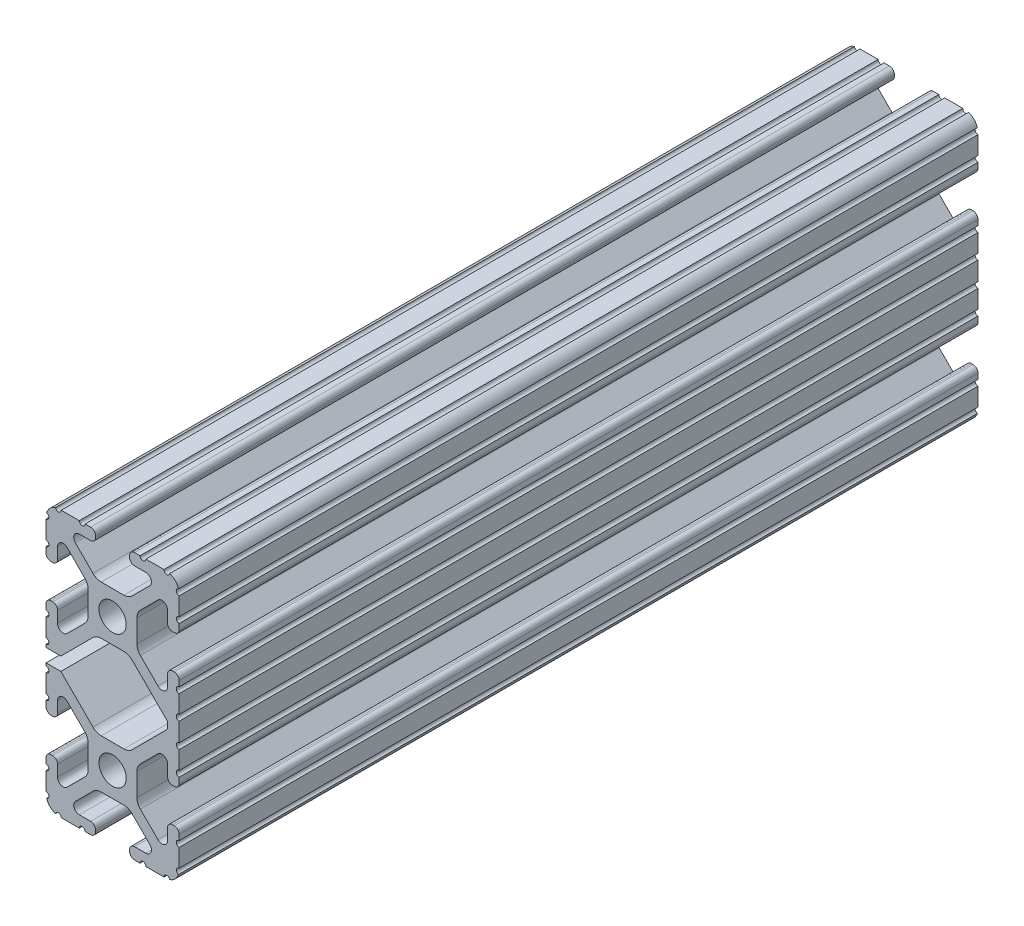
SolidWorks part; units mm, degrees
ref_plane "Front Plane" through (0, 0, 0) normal (0, 0, 1) x (1, 0, 0)
ref_plane "Top Plane" through (0, 0, 0) normal (0, 1, 0) x (1, 0, 0)
ref_plane "Right Plane" through (0, 0, 0) normal (1, 0, 0) x (0, 0, -1)
sketch "Sketch2" plane through (0, 0, 0) normal (0, 0, 1) x (1, 0, 0)
  line L0 (0, 25.4) -> (0, -25.4) construction
  line L1 (-12.7, 0) -> (12.7, 0) construction
  line L2 (3.2512, -25.4) -> (12.7, -25.4)
  line L3 (12.7, -25.4) -> (12.7, -15.9512)
  line L4 (3.2512, -25.4) -> (3.2512, -23.1902)
  line L5 (3.2512, -23.1902) -> (8.9276, -23.1902)
  line L6 (8.9276, -23.1902) -> (3.0856, -17.3482)
  line L7 (0, -12.7) -> (12.7, -25.4) construction
  line L8 (12.7, -15.9512) -> (10.4902, -15.9512)
  line L9 (10.4902, -15.9512) -> (10.4902, -21.6276)
  line L10 (10.4902, -21.6276) -> (4.6482, -15.7856)
  circle A0 centre (0, -12.7) radius 2.6035
  arc A1 (6.3485, -23.1902) -> (7.1039, -21.3665) centre (6.3485, -22.1219) ccw construction
  point P8 (0, -17.3482)
  dimension "Center Hole Diameter" = 5.207
  dimension "Rail Height" = 50.8
  dimension "Rail Width" = 25.4
  dimension "T-Slot Width" = 6.5024
  dimension "Slot Inner Width" = 14.8336
  dimension "Thickness" = 2.2098
  dimension "Slot Depth" = 5.842
  dimension "D1" = 2.2098
  dimension "C to C" = 25.4
sketch "Sketch3" plane through (0, 0, 0) normal (1, 0, 0) x (0, 0, -1)
  line L0 (-76.2, -25.4) -> (76.2, -25.4) construction
  line L1 (-50.8, 0) -> (50.8, 0) construction
  dimension "Length" = 152.4
sketch "Sketch4" plane through (0, 0, 0) normal (0, 0, 1) x (1, 0, 0)
  line L0 (4.1904, -25.4) -> (10.1173, -25.4)
  line L1 (3.2512, -25.4) -> (12.7, -25.4) construction
  line L2 (3.2512, -25.4) -> (3.2512, -23.1902) construction
  line L3 (3.2512, -23.1902) -> (8.9276, -23.1902) construction
  line L4 (3.2512, -24.1294) -> (3.2512, -24.4608)
  line L5 (4.1904, -23.1902) -> (6.3485, -23.1902)
  line L6 (0, -17.3482) -> (2.164, -17.3482)
  line L7 (8.9276, -23.1902) -> (3.0856, -17.3482) construction
  line L8 (3.7373, -17.9999) -> (7.1039, -21.3665)
  line L9 (12.7, -25.4) -> (12.7, -15.9512) construction
  line L10 (10.4902, -21.6276) -> (4.6482, -15.7856) construction
  line L11 (10.4902, -15.9512) -> (10.4902, -21.6276) construction
  line L12 (10.4902, -19.0485) -> (10.4902, -16.8904)
  line L13 (12.7, -15.9512) -> (10.4902, -15.9512) construction
  line L14 (11.4294, -15.9512) -> (11.7608, -15.9512)
  line L15 (12.7, -16.8904) -> (12.7, -22.8173)
  line L16 (8.6665, -19.8039) -> (5.2999, -16.4373)
  line L17 (4.6482, -12.7) -> (4.6482, -14.864)
  line L19 (0, -17.3482) -> (0, -15.3035)
  line L20 (0, 25.4) -> (0, -25.4) construction
  line L21 (4.6482, -12.7) -> (2.6035, -12.7)
  arc A0 (3.2512, -24.4608) -> (4.1904, -25.4) centre (4.1904, -24.4608) ccw
  circle A1 centre (0, -12.7) radius 2.6035 construction
  arc A2 (3.2512, -24.1294) -> (4.1904, -23.1902) centre (4.1904, -24.1294) cw
  arc A3 (6.3485, -23.1902) -> (7.1039, -21.3665) centre (6.3485, -22.1219) ccw
  arc A4 (2.164, -17.3482) -> (3.7373, -17.9999) centre (2.164, -19.5732) cw
  arc A5 (10.1173, -25.4) -> (12.7, -22.8173) centre (10.1173, -22.8173) ccw
  arc A6 (8.6665, -19.8039) -> (10.4902, -19.0485) centre (9.4219, -19.0485) ccw
  arc A7 (10.4902, -16.8904) -> (11.4294, -15.9512) centre (11.4294, -16.8904) cw
  arc A8 (11.7608, -15.9512) -> (12.7, -16.8904) centre (11.7608, -16.8904) cw
  arc A9 (5.2999, -16.4373) -> (4.6482, -14.864) centre (6.8732, -14.864) cw
  arc A11 (0, -15.3035) -> (2.6035, -12.7) centre (0, -12.7) ccw
  dimension "D1" = 2.5827
  dimension "D2" = 2.225
  dimension "D3" = 0.9392
extrude "Boss-Extrude1" add sketch "Sketch4" along normal mid plane 152.4
sketch "Sketch5" plane through (0, 0, 0) normal (0, 0, 1) x (1, 0, 0)
  line L0 (3.2512, -25.4) -> (12.7, -25.4) construction
  line L1 (4.1904, -23.1902) -> (6.3485, -23.1902) construction
  line L3 (0, -12.7) -> (12.7, -25.4) construction
  line L4 (6.3485, -23.1902) -> (6.3485, -25.4) construction
  line L5 (8.9276, -23.1902) -> (3.0856, -17.3482) construction
  circle A0 centre (10.3562, -25.4) radius 0.5524
  circle A1 centre (5.796, -25.4) radius 0.5524
  circle A2 centre (12.7, -23.0562) radius 0.5524
  circle A3 centre (12.7, -18.496) radius 0.5524
  point P10 (5.2694, -23.1902)
  point P12 (9.4219, -19.0485)
  dimension "D1" = 1.1049
extrude "Cut-Extrude1" cut sketch "Sketch5" against normal through all both and the other way through all
mirror "Mirror1" about plane through (4.6482, -12.7, 76.2) normal (0, -1, 0) of bodies 137 134
sketch "Sketch6" plane through (0, 0, 0) normal (0, 0, 1) x (1, 0, 0)
  line L0 (12.7, -1.7914) -> (12.7, 0)
  line L1 (12.7, 0) -> (9.8037, 0)
  line L2 (-12.7, 0) -> (12.7, 0) construction
  line L3 (9.8037, 0) -> (9.8037, -2.3438)
  line L4 (9.8037, -2.3438) -> (12.1476, -2.3438)
  circle A0 centre (12.7, -2.3438) radius 0.5524 construction
  arc A1 (12.7, -1.7914) -> (12.1476, -2.3438) centre (12.7, -2.3438) ccw
  arc A4 (12.58, -1.8046) -> (12.7, -2.8963) centre (12.7, -2.3438) ccw construction
  arc A6 (9.8037, 0) -> (10.8954, -0.12) centre (10.3562, 0) ccw construction
extrude "Boss-Extrude2" add sketch "Sketch6" along normal mid plane 152.4
sketch "Sketch7" plane through (0, 0, 0) normal (0, 0, 1) x (1, 0, 0)
  line L0 (5.4206, -5.7168) -> (10.3284, -0.809)
  line L1 (3.7373, -7.4001) -> (7.1039, -4.0335) construction
  line L2 (10.4902, -0.4184) -> (10.4902, 0)
  line L3 (0, 0) -> (10.4902, 0)
  line L4 (-12.7, 0) -> (12.7, 0) construction
  line L5 (0, 0) -> (5.4206, -5.7168)
  arc A0 (10.3284, -0.809) -> (10.4902, -0.4184) centre (9.9377, -0.4184) ccw
  arc A3 (12.7, -1.7914) -> (12.7, -2.8963) centre (12.7, -2.3438) ccw construction
extrude "Cut-Extrude2" cut sketch "Sketch7" against normal through all both and the other way through all
mirror "Mirror2" about plane through (0, 0, 0) normal (0, 1, 0) of bodies 139 135
mirror "Mirror3" about plane through (0, 0, 0) normal (1, 0, 0) of bodies 136
sketch "Sketch9" plane through (4.6482, 0, 0) normal (1, 0, 0) x (0, 0, -1)
  line L1 (-76.2, 14.864) -> (-76.2, 10.536) construction
  line L2 (0, 13.97) -> (0, -13.97) construction
  line L3 (13.97, 0) -> (-13.97, 0) construction
  circle A0 centre (-63.5, 12.7) radius 3.175
  circle A1 centre (63.5, 12.7) radius 3.175
  circle A2 centre (63.5, -12.7) radius 3.175
  circle A3 centre (-63.5, -12.7) radius 3.175
  point P4 (-76.2, 12.7)
  dimension "D2" = 6.35
extrude "Cut-Extrude3" cut sketch "Sketch9" against normal through all both and the other way through all
sketch "Sketch10" plane through (0, 0, 76.2) normal (0, 0, 1) x (1, 0, 0)
  line L0 (-12.7, -1.7914) -> (-12.7, 1.7914) construction
  line L1 (-17.9881, 1.27) -> (-7.4119, 1.27)
  line L2 (-17.9881, 1.27) -> (-17.9881, -1.27)
  line L3 (-17.9881, -1.27) -> (-7.4119, -1.27)
  line L4 (-7.4119, 1.27) -> (-7.4119, -1.27)
  line L5 (-17.9881, 1.27) -> (-7.4119, -1.27) construction
  line L6 (-17.9881, -1.27) -> (-7.4119, 1.27) construction
  point P0 (-12.7, 0)
  dimension "D1" = 2.54
extrude "Cut-Extrude5" cut sketch "Sketch10" against normal through all both and the other way through all contours L2 L3 L4 L1
equation "\"D1@Boss-Extrude1\"=\"Length@Sketch3\""
equation "\"D1@Sketch2\"=\"Thickness@Sketch2\""
equation "\"D2@Sketch4\"=\"Slot Inner Width@Sketch2\"*0.15"
equation "\"D1@Sketch4\"=\"D3@Sketch4\"*2.75"
equation "\"D3@Sketch4\"=\"Thickness@Sketch2\"*0.425"
equation "\"D1@Sketch5\"=\"Thickness@Sketch2\"*0.5"
equation "\"D1@Boss-Extrude2\"=\"Length@Sketch3\""
equation "\"testbed_height\" = 91.50mm"
equation "\"plate_thickness\" = 4mm"
equation "\"main_body_splay_length\" = 48.5mm"
equation "\"splay_shaft_length_no_wires\" = 10mm"
equation "\"splay_shaft_length_wires\" = 6.5mm"
equation "\"timing_pulley_offset\" = 0mm"
equation "\"effective_motor_length\" = \"timing_pulley_offset\" + \"splay_shaft_length_no_wires\" + \"main_body_splay_length\""
equation "\"80_20_side\" = 25.4mm"
equation "\"80_20_length\" = 152.4mm"
equation "\"80_20_optic_mount_length\" = \"80_20_length\" - 25.4mm"
equation "\"optic_board_hole_size\" = 6.35mm"
equation "\"total_mounting_length\" = \"testbed_height\" - \"effective_motor_length\" - \"80_20_side\""
equation "\"mounting_vertical_portion_height\" = \"total_mounting_length\" - 2 * \"plate_thickness\""
equation "\"face_mount_width\" = 15.25mm"
equation "\"center_dist_to_face_mount_vertical_screws\" = 5mm"
equation "\"D2@Sketch9\"=\"optic_board_hole_size\""
equation "\"D1@Sketch9\"=\"80_20_optic_mount_length\"/2"
